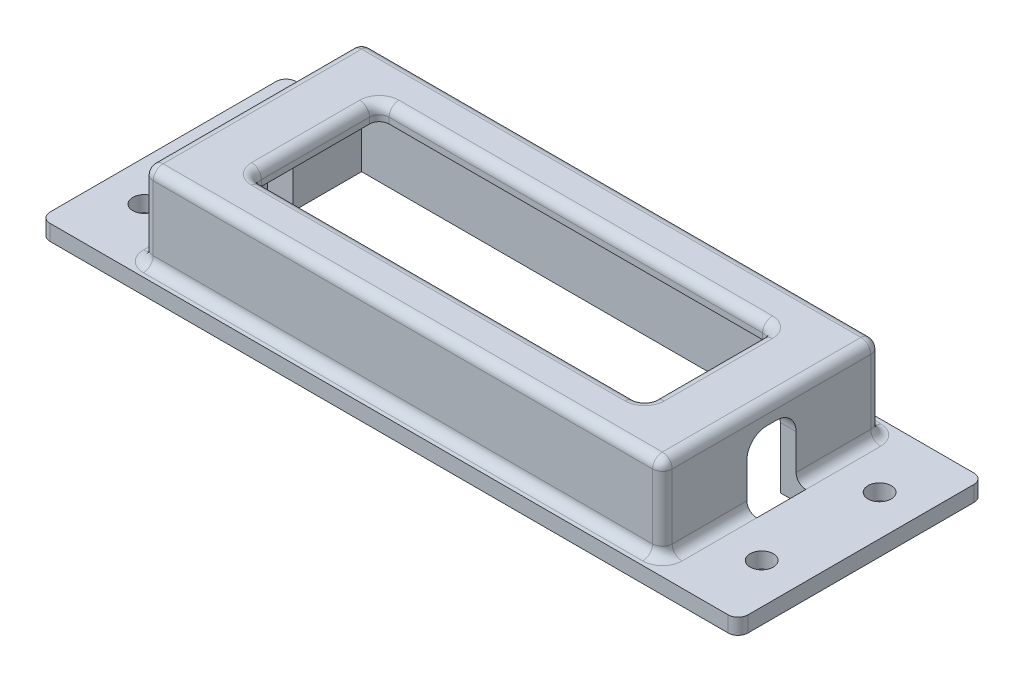
SolidWorks part; units mm, degrees
ref_plane "Front Plane" through (0, 0, 0) normal (0, 0, 1) x (1, 0, 0)
ref_plane "Top Plane" through (0, 0, 0) normal (0, 1, 0) x (1, 0, 0)
ref_plane "Right Plane" through (0, 0, 0) normal (1, 0, 0) x (0, 0, -1)
sketch "Sketch1" plane through (0, 0, 0) normal (0, 1, 0) x (1, 0, 0)
  line L1 (-31.496, 12.065) -> (31.496, 12.065)
  line L2 (-31.496, 12.065) -> (-31.496, -12.065)
  line L3 (-31.496, -12.065) -> (31.496, -12.065)
  line L4 (31.496, 12.065) -> (31.496, -12.065)
  line L5 (-31.496, 12.065) -> (31.496, -12.065) construction
  line L6 (-31.496, -12.065) -> (31.496, 12.065) construction
  point P0 (0, 0)
  dimension "D1" = 62.992
  dimension "D2" = 24.13
extrude "Boss-Extrude1" add sketch "Sketch1" along normal blind 8.89
shell "Shell1" thickness 2.032 removed face at (0, 0, 0) outward yes
sketch "Sketch2" plane through (-33.528, 0, 0) normal (-1, 0, 0) x (0, 0, 1)
  line L0 (0, 0) -> (0, 10.922) construction
  line L1 (-14.097, 0) -> (14.097, 0) construction
  line L2 (-14.097, 10.922) -> (14.097, 10.922) construction
  line L4 (-3.175, 0) -> (3.175, 0)
  line L5 (-3.175, 0) -> (-3.175, 5.842)
  line L6 (-3.175, 5.842) -> (3.175, 5.842)
  line L7 (3.175, 0) -> (3.175, 5.842)
  dimension "D1" = 5.842
  dimension "D2" = 6.35
  dimension "D3" = 3.175
extrude "Cut-Extrude1" cut sketch "Sketch2" against normal blind 8.89
sketch "Sketch3" plane through (33.528, 0, 0) normal (1, 0, 0) x (0, 0, -1)
  line L0 (0, 0) -> (0, 10.922) construction
  line L1 (-14.097, 10.922) -> (14.097, 10.922) construction
  line L2 (-14.097, 0) -> (14.097, 0) construction
  line L3 (-3.175, 0) -> (3.175, 0)
  line L4 (-3.175, 0) -> (-3.175, 8.382)
  line L5 (-3.175, 8.382) -> (3.175, 8.382)
  line L6 (3.175, 0) -> (3.175, 8.382)
  dimension "D1" = 6.35
  dimension "D2" = 3.175
  dimension "D3" = 8.382
extrude "Cut-Extrude2" cut sketch "Sketch3" against normal blind 8.89
fillet "Fillet1" radius 2.54 4 edges at (-32.512, 5.842, 3.175) (-32.512, 5.842, -3.175) (32.512, 8.382, -3.175) (32.512, 8.382, 3.175)
sketch "Sketch4" plane through (0, 0, 0) normal (0, -1, 0) x (1, 0, 0)
  line L0 (45.9737, 0) -> (-47.055, 0) construction
  line L1 (0, 20.7124) -> (0, -23.2033) construction
  line L3 (-33.528, 3.175) -> (-33.528, 14.097) construction
  line L5 (-45.085, 15.875) -> (45.085, 15.875)
  line L6 (-45.085, 15.875) -> (-45.085, -15.875)
  line L7 (-45.085, -15.875) -> (45.085, -15.875)
  line L8 (45.085, 15.875) -> (45.085, -15.875)
  line L9 (-45.085, 15.875) -> (45.085, -15.875) construction
  line L10 (-45.085, -15.875) -> (45.085, 15.875) construction
  circle A0 centre (-39.878, 7.62) radius 1.5
  circle A1 centre (-39.878, -7.62) radius 1.5
  circle A2 centre (39.878, -7.62) radius 1.5
  circle A3 centre (39.878, 7.62) radius 1.5
  point P11 (0, 0)
  dimension "D1" = 3
  dimension "D2" = 7.62
  dimension "D3" = 6.35
  dimension "D4" = 90.17
  dimension "D5" = 31.75
extrude "Boss-Extrude2" add sketch "Sketch4" along normal blind 2.032
sketch "Sketch5" plane through (0, -2.032, 0) normal (0, -1, 0) x (1, 0, 0)
  line L1 (-31.496, 12.065) -> (31.496, 12.065)
  line L2 (-31.496, 12.065) -> (-31.496, -12.065)
  line L3 (-31.496, -12.065) -> (31.496, -12.065)
  line L4 (31.496, 12.065) -> (31.496, -12.065)
  line L5 (-31.496, 12.065) -> (31.496, -12.065) construction
  line L6 (-31.496, -12.065) -> (31.496, 12.065) construction
  point P0 (0, 0)
  dimension "D1" = 24.13
  dimension "D2" = 62.992
extrude "Cut-Extrude3" cut sketch "Sketch5" against normal blind 10.922
fillet "Fillet2" radius 1.27 18 edges at (0, 10.922, 14.097) (-33.528, 10.922, 0) (0, 10.922, -14.097) (33.528, 10.922, 0) (-45.085, -1.016, 15.875) (-45.085, -1.016, -15.875) (45.085, -1.016, -15.875) (45.085, -1.016, 15.875) (-33.528, 5.461, -14.097) (-33.528, 5.461, 14.097) (33.528, 5.461, 14.097) (33.528, 5.461, -14.097) (0, 0, -14.097) (33.528, 0, -8.636) (33.528, 0, 8.636) (0, 0, 14.097) (-33.528, 0, 8.636) (-33.528, 0, -8.636)
sketch "Sketch6" plane through (0, 10.922, 0) normal (0, 1, 0) x (1, 0, 0)
  line L1 (-25.4, 8.255) -> (25.4, 8.255)
  line L2 (-25.4, 8.255) -> (-25.4, -8.255)
  line L3 (-25.4, -8.255) -> (25.4, -8.255)
  line L4 (25.4, 8.255) -> (25.4, -8.255)
  line L5 (-25.4, 8.255) -> (25.4, -8.255) construction
  line L6 (-25.4, -8.255) -> (25.4, 8.255) construction
  point P0 (0, 0)
  dimension "D1" = 16.51
  dimension "D2" = 50.8
extrude "Cut-Extrude4" cut sketch "Sketch6" against normal blind 10.922
fillet "Fillet3" radius 1.27 8 edges at (-25.4, 10.922, 0) (0, 10.922, 8.255) (0, 10.922, -8.255) (25.4, 10.922, 0) (25.4, 9.906, -8.255) (25.4, 9.906, 8.255) (-25.4, 9.906, -8.255) (-25.4, 9.906, 8.255)
sketch "Sketch8" plane through (0, 0, 0) normal (0, 1, 0) x (1, 0, 0)
  line L1 (-31.496, -3.175) -> (-34.798, -3.175)
  line L2 (-31.496, -3.175) -> (-31.496, 3.175)
  line L3 (-31.496, 3.175) -> (-34.798, 3.175)
  line L4 (-34.798, -3.175) -> (-34.798, 3.175)
  line L5 (34.798, 3.175) -> (31.496, 3.175)
  line L6 (34.798, 3.175) -> (34.798, -3.175)
  line L7 (34.798, -3.175) -> (31.496, -3.175)
  line L8 (31.496, 3.175) -> (31.496, -3.175)
extrude "Cut-Extrude5" cut sketch "Sketch8" against normal blind 10.922
